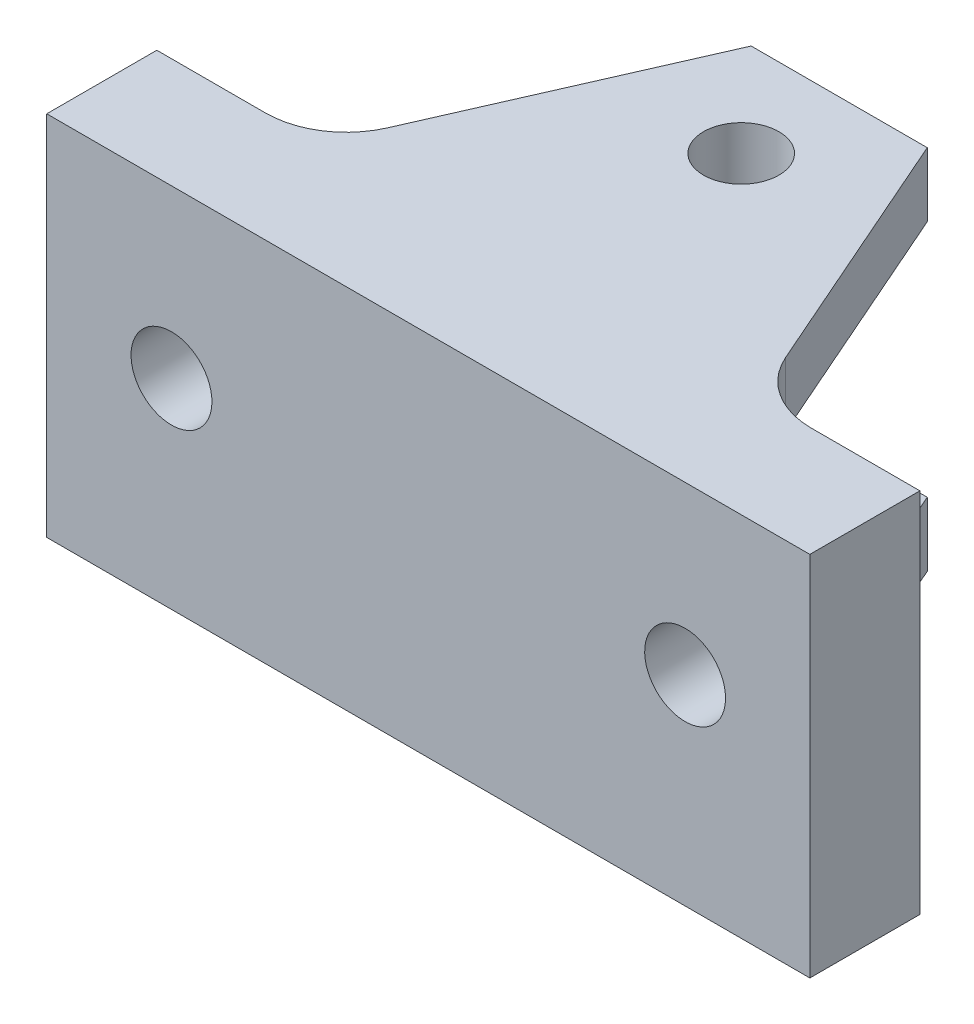
SolidWorks part; units mm, degrees
material "Custom Plastic"
ref_plane "X-Y Datum" through (0, 0, 0) normal (0, 0, 1) x (1, 0, 0)
ref_plane "X-Z Datum" through (0, 0, 0) normal (0, 1, 0) x (1, 0, 0)
ref_plane "Y-Z Datum" through (0, 0, 0) normal (1, 0, 0) x (0, 0, -1)
sketch "Sketch1" plane through (0, 0, 0) normal (1, 0, 0) x (0, 0, -1)
  line L0 (0, 8.7126) -> (0, 40.4626)
  line L1 (0, 40.4626) -> (39.7797, 40.4626)
  line L2 (39.7797, 40.4626) -> (39.7797, 34.9127)
  line L3 (39.7797, 34.9127) -> (9.525, 34.9127)
  line L4 (9.525, 34.9127) -> (9.525, 14.2625)
  line L5 (9.525, 14.2625) -> (39.7797, 14.2625)
  line L6 (39.7797, 14.2625) -> (39.7797, 8.7126)
  line L7 (39.7797, 8.7126) -> (0, 8.7126)
  line L8 (29.6197, 40.4626) -> (29.6197, 8.7126) construction
  line L9 (0, 26.0299) -> (9.525, 26.0299) construction
  line L10 (0, 22.0299) -> (0, 30.0299) construction
  circle A0 centre (29.6197, 24.5876) radius 10.3251 construction
  dimension "D5" = 20.6502
  dimension "D1" = 20.6502
  dimension "D2" = 31.75
  dimension "D3" = 10.16
  dimension "D4" = 9.525
extrude "Boss-Extrude1" add sketch "Sketch1" along normal blind 76.2
sketch "Sketch2" plane through (0, 0, -9.525) normal (0, 0, -1) x (-1, 0, 0)
  line L0 (-38.1, 34.9127) -> (-38.1, 14.2625) construction
  line L1 (-76.2, 34.9127) -> (0, 34.9127) construction
  line L2 (-76.2, 14.2625) -> (0, 14.2625) construction
  line L3 (-60.325, 26.0299) -> (-15.875, 26.0299) construction
  circle A0 centre (-60.325, 26.0299) radius 3.4
  circle A1 centre (-15.875, 26.0299) radius 3.4
  point P8 (-38.1, 26.0299)
  dimension "D2" = 6.8
  dimension "D1" = 44.45
extrude "Cut-Extrude1" cut sketch "Sketch2" against normal up to surface (9.525 mm away) up to face at (38.1, 24.5876, 0)
sketch "Sketch3" plane through (0, 40.4626, 0) normal (0, 1, 0) x (1, 0, 0)
  line L0 (76.2, 39.7797) -> (0, 39.7797) construction
  line L1 (30.48, 35.56) -> (19.05, 9.525)
  line L2 (45.72, 35.56) -> (57.15, 9.525)
  line L3 (30.48, 35.56) -> (45.72, 35.56)
  line L4 (0, 39.7797) -> (0, 9.525)
  line L5 (0, 0) -> (0, 39.7797) construction
  line L6 (0, 9.525) -> (19.05, 9.525)
  line L7 (0, 39.7797) -> (76.2, 39.7797)
  line L8 (76.2, 39.7797) -> (76.2, 9.525)
  line L9 (76.2, 39.7797) -> (76.2, 0) construction
  line L10 (76.2, 9.525) -> (57.15, 9.525)
  line L12 (76.2, 0) -> (0, 0) construction
  circle A0 centre (38.1, 27.0797) radius 3.2639
  point P4 (38.1, 39.7797)
  dimension "D1" = 6.5278
  dimension "D2" = 12.7
  dimension "D3" = 15.24
  dimension "D4" = 35.56
  dimension "D5" = 19.05
extrude "Cut-Extrude2" cut sketch "Sketch3" against normal up to surface (31.75 mm away) up to face at (38.1, 8.7126, -19.8899)
sketch "Sketch4" plane through (0, 0, -9.525) normal (0, 0, -1) x (-1, 0, 0)
  line L0 (0, 40.4626) -> (-19.05, 40.4626) construction
  line L1 (0, 8.7126) -> (-5.08, 8.7126)
  line L2 (0, 8.7126) -> (0, 40.4626)
  line L3 (0, 40.4626) -> (-5.08, 40.4626)
  line L4 (-5.08, 8.7126) -> (-5.08, 40.4626)
  line L5 (-57.15, 40.4626) -> (-76.2, 40.4626) construction
  line L6 (-76.2, 8.7126) -> (-71.12, 8.7126)
  line L7 (-76.2, 8.7126) -> (-76.2, 40.4626)
  line L8 (-76.2, 40.4626) -> (-71.12, 40.4626)
  line L9 (-71.12, 8.7126) -> (-71.12, 40.4626)
  dimension "D1" = 5.08
extrude "Cut-Extrude3" cut sketch "Sketch4" against normal up to surface (9.525 mm away) up to face at (60.325, 29.4299, 0)
fillet "Fillet1" radius 6.985 4 edges at (57.15, 37.6877, -9.525) (57.15, 11.4876, -9.525) (19.05, 37.6877, -9.525) (19.05, 11.4876, -9.525)
sketch "Sketch5" plane through (0, 0, -9.525) normal (0, 0, -1) x (-1, 0, 0)
  circle A0 centre (-60.325, 26.0299) radius 3.5
  circle A1 centre (-15.875, 26.0299) radius 3.5
  dimension "D1" = 7
extrude "Cut-Extrude4" cut sketch "Sketch5" against normal through all both and the other way through all
